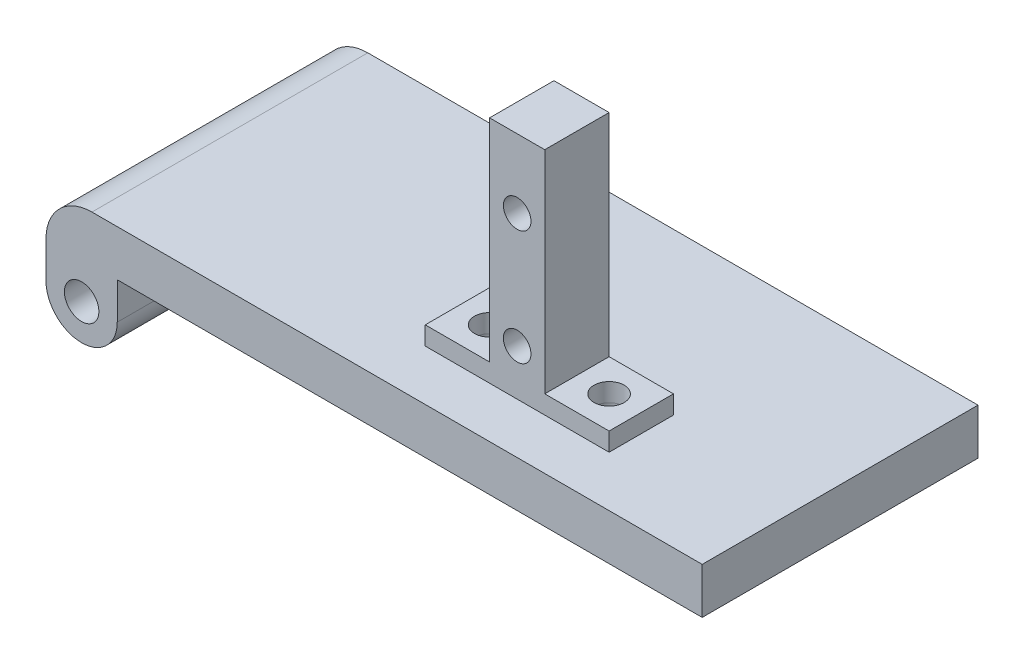
SolidWorks part; units mm, degrees
other "Lever Arm"
other "Motor Mount"
ref_plane "Front Plane" through (0, 0, 0) normal (0, 0, 1) x (1, 0, 0)
ref_plane "Top Plane" through (0, 0, 0) normal (0, 1, 0) x (1, 0, 0)
ref_plane "Right Plane" through (0, 0, 0) normal (1, 0, 0) x (0, 0, -1)
sketch "Sketch1" plane through (0, 0, 0) normal (0, 0, 1) x (1, 0, 0)
  line L0 (-38.9731, -8.255) -> (-38.9731, -3.175)
  line L1 (-38.9731, 3.175) -> (38.9731, 3.175)
  line L2 (-38.9731, 3.175) -> (-38.9731, -3.175)
  line L3 (-29.1306, -3.175) -> (38.9731, -3.175)
  line L4 (38.9731, 3.175) -> (38.9731, -3.175)
  line L5 (-38.9731, 3.175) -> (38.9731, -3.175) construction
  line L6 (-38.9731, -3.175) -> (38.9731, 3.175) construction
  line L7 (-29.1306, -8.255) -> (-29.1306, -3.175)
  circle A0 centre (-34.0519, -8.255) radius 2.3812
  arc A1 (-38.9731, -8.255) -> (-29.1306, -8.255) centre (-34.0519, -8.255) ccw
  point P0 (0, 0)
  dimension "D1" = 4.7625
  dimension "D3" = 2.54
  dimension "D2" = 6.35
  dimension "D4" = 73.025
  dimension "D5" = 5.08
extrude "Boss-Extrude1" add sketch "Sketch1" along normal blind 38.1
fillet "Fillet1" radius 6.35 1 edges at (-38.9731, 3.175, 19.05)
sketch "Sketch3" plane through (38.9731, 0, 0) normal (1, 0, 0) x (0, 0, -1)
  line L4 (0, -3.175) -> (0, 3.175)
  line L5 (0, 3.175) -> (-38.1, 3.175)
  line L6 (-38.1, 3.175) -> (-38.1, -3.175)
  line L7 (-38.1, -3.175) -> (0, -3.175)
  line L8 (0, -3.175) -> (0, 3.175)
  line L9 (0, 3.175) -> (-38.1, 3.175)
  line L10 (-38.1, 3.175) -> (-38.1, -3.175)
  line L11 (-38.1, -3.175) -> (0, -3.175)
  dimension "D1" = 0
extrude "Boss-Extrude2" add sketch "Sketch3" along normal blind 12.7
sketch "Sketch2" plane through (0, 3.175, 0) normal (0, 1, 0) x (1, 0, 0)
  line L1 (50.0856, -22.225) -> (13.5731, -22.225) construction
  line L2 (50.0856, -22.225) -> (50.0856, 0) construction
  line L3 (50.0856, 0) -> (13.5731, 0) construction
  line L4 (13.5731, -22.225) -> (13.5731, 0) construction
  line L5 (50.0856, -22.225) -> (13.5731, 0) construction
  line L6 (50.0856, 0) -> (13.5731, -22.225) construction
  line L7 (13.5731, -20.6375) -> (-15.0019, -20.6375) construction
  line L8 (13.5731, -20.6375) -> (13.5731, -1.5875) construction
  line L9 (13.5731, -1.5875) -> (-15.0019, -1.5875) construction
  line L10 (-15.0019, -20.6375) -> (-15.0019, -1.5875) construction
  line L11 (13.5731, -20.6375) -> (-15.0019, -1.5875) construction
  line L12 (13.5731, -1.5875) -> (-15.0019, -20.6375) construction
  line L13 (38.9731, -28.575) -> (38.9731, 6.35) construction
  line L14 (51.6731, 0) -> (-32.6231, 0) construction
  line L15 (-36.4331, -38.1) -> (-31.6706, -38.1) construction
  line L16 (-36.4331, -38.1) -> (-31.6706, -38.1) construction
  line L18 (22.9394, -31.115) -> (15.3194, -31.115)
  line L19 (22.9394, -31.115) -> (22.9394, -22.225)
  line L20 (22.9394, -22.225) -> (15.3194, -22.225)
  line L21 (15.3194, -31.115) -> (15.3194, -22.225)
  line L22 (22.9394, -31.115) -> (15.3194, -22.225) construction
  line L23 (22.9394, -22.225) -> (15.3194, -31.115) construction
  point P0 (31.8294, -11.1125)
  point P5 (19.1294, -26.67)
  point P6 (-0.7144, -11.1125)
  point P15 (19.1294, -26.67)
  point P21 (-34.0519, -38.1)
  point P26 (38.9731, -11.1125)
  dimension "D1" = 22.225
  dimension "D2" = 36.5125
  dimension "D3" = 28.575
  dimension "D4" = 19.05
  dimension "D5" = 5.5562
  dimension "D6" = 11.1125
  dimension "D7" = 34.925
  dimension "D8" = 73.025
  dimension "D9" = 8.89
  dimension "D10" = 7.62
extrude "Boss-Extrude3" add sketch "Sketch2" along normal blind 31.75
sketch "Sketch5" plane through (0, 0, 31.115) normal (0, 0, 1) x (1, 0, 0)
  line L0 (19.1294, 34.925) -> (19.1294, 3.175) construction
  line L1 (15.3194, 34.925) -> (22.9394, 34.925) construction
  line L2 (15.3194, 3.175) -> (22.9394, 3.175) construction
  circle A0 centre (19.1294, 9.525) radius 1.905
  circle A1 centre (19.1294, 25.4) radius 1.905
  dimension "D1" = 3.81
  dimension "D2" = 15.875
  dimension "D3" = 6.35
extrude "Cut-Extrude1" cut sketch "Sketch5" against normal through all both and the other way through all
sketch "Sketch6" plane through (0, 3.175, 0) normal (0, 1, 0) x (1, 0, 0)
  line L0 (15.3194, -31.115) -> (22.9394, -31.115) construction
  line L1 (31.8294, -31.115) -> (6.4294, -31.115)
  line L2 (31.8294, -31.115) -> (31.8294, -22.225)
  line L3 (31.8294, -22.225) -> (6.4294, -22.225)
  line L4 (6.4294, -31.115) -> (6.4294, -22.225)
  line L5 (31.8294, -31.115) -> (6.4294, -22.225) construction
  line L6 (31.8294, -22.225) -> (6.4294, -31.115) construction
  line L7 (22.9394, -22.225) -> (15.3194, -22.225) construction
  line L8 (17.2244, -31.115) -> (21.0344, -31.115) construction
  line L9 (17.2244, -31.115) -> (21.0344, -31.115) construction
  line L10 (15.3194, -22.225) -> (15.3194, -31.115) construction
  point P0 (19.1294, -26.67)
  point P14 (19.1294, -31.115)
  dimension "D1" = 25.4
  dimension "D2" = 8.89
  dimension "D3" = 8.89
extrude "Boss-Extrude4" add sketch "Sketch6" along normal blind 2.54
sketch "Sketch7" plane through (0, 5.715, 0) normal (0, 1, 0) x (1, 0, 0)
  line L0 (6.4294, -31.115) -> (31.8294, -31.115) construction
  line L1 (15.3194, -31.115) -> (6.4294, -31.115) construction
  line L2 (15.3194, -31.115) -> (15.3194, -22.225) construction
  line L3 (15.3194, -22.225) -> (6.4294, -22.225) construction
  line L4 (6.4294, -31.115) -> (6.4294, -22.225) construction
  line L5 (15.3194, -31.115) -> (6.4294, -22.225) construction
  line L6 (15.3194, -22.225) -> (6.4294, -31.115) construction
  line L7 (15.3194, -22.225) -> (15.3194, -31.115) construction
  line L8 (17.2244, -31.115) -> (21.0344, -31.115) construction
  line L9 (17.2244, -31.115) -> (21.0344, -31.115) construction
  line L10 (19.1294, -31.115) -> (19.1294, -22.225) construction
  line L11 (31.8294, -22.225) -> (6.4294, -22.225) construction
  circle A0 centre (10.8744, -26.67) radius 2.0828
  circle A2 centre (27.3844, -26.67) radius 2.0828
  point P14 (19.1294, -31.115)
  dimension "D1" = 4.1656
extrude "Cut-Extrude2" cut sketch "Sketch7" against normal through all both and the other way through all
split "Split1" bodies to split 106 resulting bodies 107 108 split by face at (9.525, 3.175, 19.05)
